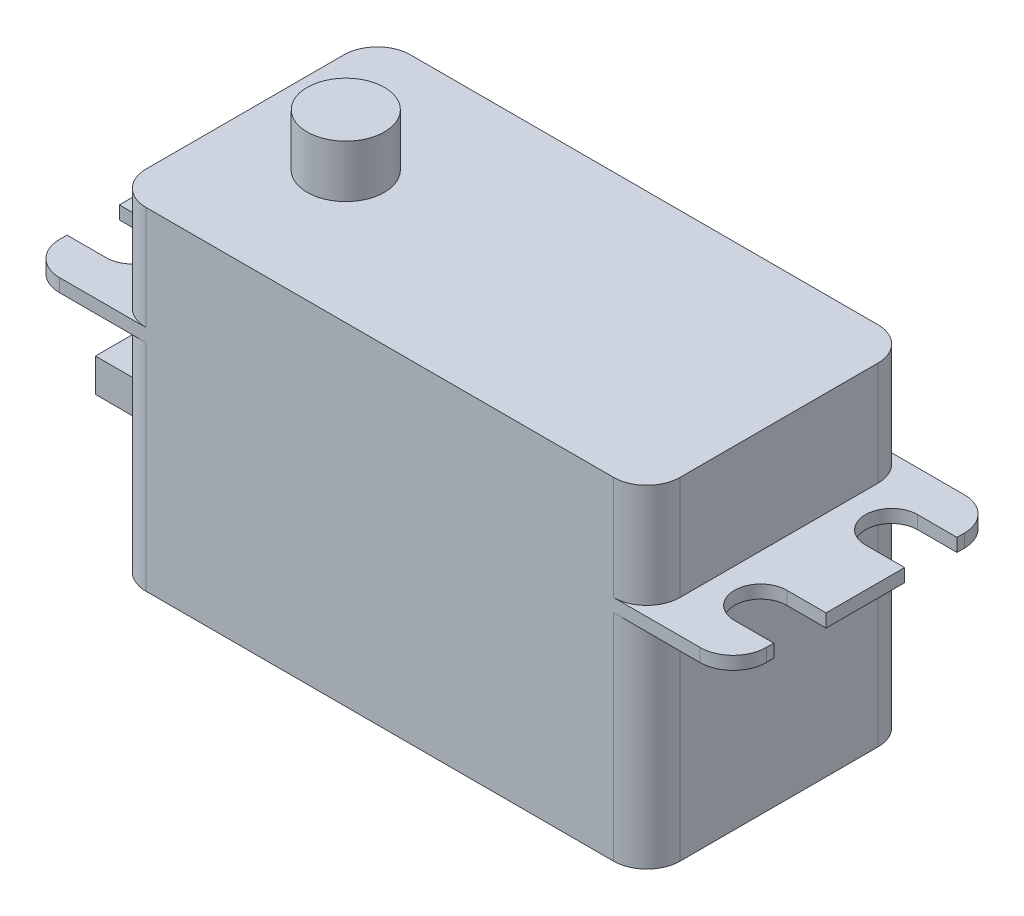
SolidWorks part; units mm, degrees
ref_plane "Front Plane" through (0, 0, 0) normal (0, 0, 1) x (1, 0, 0)
ref_plane "Top Plane" through (0, 0, 0) normal (0, 1, 0) x (1, 0, 0)
ref_plane "Right Plane" through (0, 0, 0) normal (1, 0, 0) x (0, 0, -1)
sketch "Sketch1" plane through (0, 0, 0) normal (0, 1, 0) x (1, 0, 0)
  line L0 (-16.17, 0) -> (16.17, 0) construction
  line L1 (-24.46, -10.1) -> (24.46, -10.1)
  line L2 (-27, -7.56) -> (-27, 7.56)
  line L3 (-24.46, 10.1) -> (24.46, 10.1)
  line L4 (27, -7.56) -> (27, 7.56)
  line L5 (-27, -10.1) -> (27, 10.1) construction
  line L6 (-27, 10.1) -> (27, -10.1) construction
  line L7 (0, -11.11) -> (0, 11.11) construction
  line L8 (24, 3) -> (27, 3)
  line L9 (24, 7) -> (27, 7)
  line L10 (27, 7) -> (27, 3)
  line L11 (24, -3) -> (27, -3)
  line L12 (24, -7) -> (27, -7)
  line L13 (27, -7) -> (27, -3)
  line L14 (-24, 7) -> (-27, 7)
  line L15 (-24, 3) -> (-27, 3)
  line L16 (-27, 3) -> (-27, 7)
  line L17 (-24, -7) -> (-27, -7)
  line L18 (-24, -3) -> (-27, -3)
  line L19 (-27, -3) -> (-27, -7)
  arc A0 (24, 7) -> (24, 3) centre (24, 5) ccw
  arc A1 (24, -7) -> (24, -3) centre (24, -5) cw
  arc A2 (-24, -7) -> (-24, -3) centre (-24, -5) ccw
  arc A3 (-24, 7) -> (-24, 3) centre (-24, 5) cw
  arc A4 (-24.46, -10.1) -> (-27, -7.56) centre (-24.46, -7.56) cw
  arc A5 (24.46, -10.1) -> (27, -7.56) centre (24.46, -7.56) ccw
  arc A6 (24.46, 10.1) -> (27, 7.56) centre (24.46, 7.56) cw
  arc A7 (-27, 7.56) -> (-24.46, 10.1) centre (-24.46, 7.56) cw
  point P0 (0, 0)
  dimension "D3" = 4
  dimension "D6" = 2.54
  dimension "D1" = 54
  dimension "D2" = 20.2
  dimension "D4" = 48
  dimension "D5" = 10
extrude "Boss-Extrude1" add sketch "Sketch1" along normal blind 1 contours A7 L2 L14 A3 L15 L18 A2 L17 A4 L1 A5 L4 L12 A1 L11 L8 A0 L9 A6 L3 region at (0, 0, 0)
sketch "Sketch3" plane through (0, 1, 0) normal (0, 1, 0) x (1, 0, 0)
  line L1 (-17.86, -10.1) -> (17.86, -10.1)
  line L2 (-20.4, -7.56) -> (-20.4, 7.56)
  line L3 (-17.86, 10.1) -> (17.86, 10.1)
  line L4 (20.4, -7.56) -> (20.4, 7.56)
  line L5 (-20.4, -10.1) -> (20.4, 10.1) construction
  line L6 (-20.4, 10.1) -> (20.4, -10.1) construction
  arc A0 (-17.86, -10.1) -> (-20.4, -7.56) centre (-17.86, -7.56) cw
  arc A1 (17.86, -10.1) -> (20.4, -7.56) centre (17.86, -7.56) ccw
  arc A2 (17.86, 10.1) -> (20.4, 7.56) centre (17.86, 7.56) cw
  arc A3 (-20.4, 7.56) -> (-17.86, 10.1) centre (-17.86, 7.56) cw
  point P0 (0, 0)
  dimension "D3" = 2.54
  dimension "D1" = 40.8
  dimension "D2" = 20.2
extrude "Boss-Extrude2" add sketch "Sketch3" along normal blind 7.95
sketch "Sketch4" plane through (0, 0, 0) normal (0, -1, 0) x (1, 0, 0)
  line L1 (-17.86, -10.1) -> (17.86, -10.1)
  line L2 (-20.4, -7.56) -> (-20.4, 7.56)
  line L3 (-17.86, 10.1) -> (17.86, 10.1)
  line L4 (20.4, -7.56) -> (20.4, 7.56)
  line L5 (-20.4, -10.1) -> (20.4, 10.1) construction
  line L6 (-20.4, 10.1) -> (20.4, -10.1) construction
  arc A0 (-17.86, -10.1) -> (-20.4, -7.56) centre (-17.86, -7.56) cw
  arc A1 (17.86, -10.1) -> (20.4, -7.56) centre (17.86, -7.56) ccw
  arc A2 (17.86, 10.1) -> (20.4, 7.56) centre (17.86, 7.56) cw
  arc A3 (-20.4, 7.56) -> (-17.86, 10.1) centre (-17.86, 7.56) cw
  point P0 (0, 0)
  dimension "D3" = 2.54
  dimension "D1" = 20.2
  dimension "D2" = 40.8
extrude "Boss-Extrude3" add sketch "Sketch4" along normal blind 16.45
sketch "Sketch5" plane through (-20.4, 0, 0) normal (-1, 0, 0) x (0, 0, 1)
  line L0 (-0.8843, -9.5287) -> (-0.8843, -11.2259)
  line L1 (-3.81, -11.6473) -> (3.81, -11.6473)
  line L2 (-3.81, -11.6473) -> (-3.81, -9.1073)
  line L3 (-3.81, -9.1073) -> (3.81, -9.1073)
  line L4 (3.81, -11.6473) -> (3.81, -9.1073)
  line L5 (-3.4243, -9.5287) -> (-1.6557, -9.5287)
  line L6 (-3.4243, -9.5287) -> (-3.4243, -11.2259)
  line L7 (-3.4243, -11.2259) -> (-1.6557, -11.2259)
  line L8 (-1.6557, -9.5287) -> (-1.6557, -11.2259)
  line L9 (-0.8843, -9.5287) -> (0.8843, -9.5287)
  line L10 (0.8843, -9.5287) -> (0.8843, -11.2259)
  line L11 (-0.8843, -11.2259) -> (0.8843, -11.2259)
  line L12 (1.6557, -9.5287) -> (1.6557, -11.2259)
  line L13 (1.6557, -9.5287) -> (3.4243, -9.5287)
  line L14 (3.4243, -9.5287) -> (3.4243, -11.2259)
  line L15 (1.6557, -11.2259) -> (3.4243, -11.2259)
  point P8 (0, -11.6473)
  point P18 (-3.4243, -10.3773)
  point P19 (-3.81, -10.3773)
  point P20 (0, -11.2259)
  dimension "D2" = 2.54
  dimension "D3" = 2.54
  dimension "D4" = 7.62
  dimension "D1" = 3
extrude "Boss-Extrude4" add sketch "Sketch5" along normal blind 7.62
sketch "Sketch6" plane through (0, 8.95, 0) normal (0, 1, 0) x (1, 0, 0)
  circle A0 centre (-12.7, 0) radius 2.95
  dimension "D1" = 5.9
  dimension "D2" = 12.7
extrude "Boss-Extrude5" add sketch "Sketch6" along normal blind 4
other "CPoint1" parameters "Diameter"=25.4, "StubLength"=38.1
ref_axis "Axis1" through (-38.02, -11.2259, -3.4243) along (1, 0, 0)
other "CPoint2" parameters "Diameter"=25.4, "StubLength"=38.1
ref_axis "Axis2" through (-38.02, -11.2259, -0.8843) along (1, 0, 0)
other "CPoint3" parameters "Diameter"=25.4, "StubLength"=38.1
ref_axis "Axis3" through (-38.02, -11.2259, 1.6557) along (1, 0, 0)
equation "\"Bodytube_OD\" = 6.17in"
equation "\"Bodytube_ID\" = 5.998in"
equation "\"Motor_OD\" = 4in"
equation "\"Fwd_Tube_Length\" = 40in"
equation "\"Mid_Tube_Length\" = 1in"
equation "\"Aft_Section_Length\"= 39in"
equation "\"AB_Coupler_OD_Length\"= 1in"
equation "\"AB_Coupling_Section_Length\"= 0.375in"
equation "\"AB_Coupler_Length\"= \"AB_Coupler_OD_Length\" + \"AB_Coupling_Section_Length\" * 2"
equation "\"Cutout_Angle\" = 80"
equation "\"AB_Paddle_Height\" = 0.375in"
equation "\"AB_Coupler_Num_Screws\"= 6"
equation "\"Num_Cutouts\" = 3"
equation "\"AB_Coupler_OD\"= 6.17in"
equation "\"AB_Coupler_ID\"= 5.75in"
equation "\"AB_Coupler_Surface_Diameter\"= 5.998in"
equation "\"AB_Coupling_Screw_Diameter\"= 0.1065in"
equation "\"AB_Central_Bushing_Length\" = .75in"
equation "\"Lead_Screw_Dist\" = 3.4in"
equation "\"Lead_Screw_Diam\" = 11mm"
equation "\"Paddle_Pin_Offset\" = .25in"
equation "\"Paddle_Pin_Radius\" = 2.25in"
equation "\"Paddle_Gear_OD\" = 3.2in"
equation "\"Drive_Gear_OD\" = 1.7in"
equation "\"Fwd_BKHD_From_Top\" = 18in"
equation "\"Fin_Thickness\"= .118in"
equation "\"Guiderail_Cutout_Diameter\"= 1.5in"
equation "\"DB9_Hole_Dist\" = 25mm"
equation "\"Airbrakes_Wire_Hole_Dia\" = .25in"
equation "\"Airbrakes_Wire_Hole_Dist\" = 1.1in"
equation "\"Servo_Gear_Offset\" = 0.5in"
equation "\"D2@Sketch6\"=\"Servo_Gear_Offset\""
